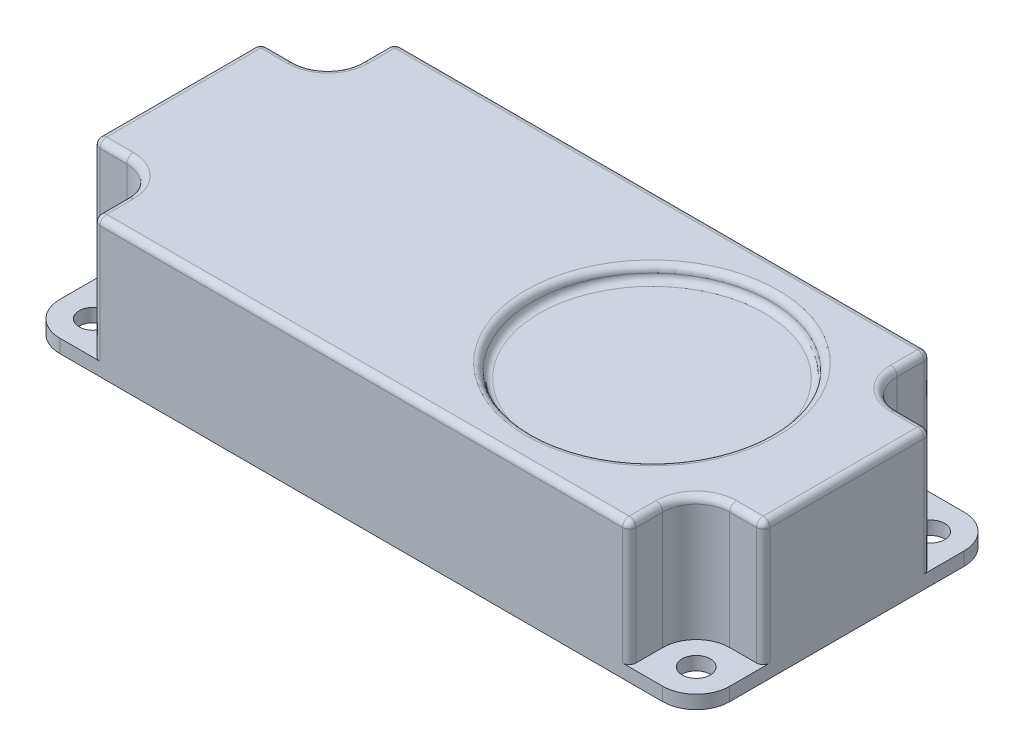
SolidWorks part; units mm, degrees
ref_plane "前视基准面" through (0, 0, 0) normal (0, 0, 1) x (1, 0, 0)
ref_plane "上视基准面" through (0, 0, 0) normal (0, 1, 0) x (1, 0, 0)
ref_plane "右视基准面" through (0, 0, 0) normal (1, 0, 0) x (0, 0, -1)
other "Configuration Table"
sketch "草图1" plane through (0, 0, 0) normal (0, 1, 0) x (1, 0, 0)
  line L1 (-45, -22.5) -> (45, -22.5)
  line L2 (-50, -17.5) -> (-50, 17.5)
  line L3 (-45, 22.5) -> (45, 22.5)
  line L4 (50, -17.5) -> (50, 17.5)
  line L5 (-50, -22.5) -> (50, 22.5) construction
  line L6 (-50, 22.5) -> (50, -22.5) construction
  arc A0 (45, -22.5) -> (50, -17.5) centre (45, -17.5) ccw
  arc A1 (-45, -22.5) -> (-50, -17.5) centre (-45, -17.5) cw
  arc A2 (-50, 17.5) -> (-45, 22.5) centre (-45, 17.5) cw
  arc A3 (45, 22.5) -> (50, 17.5) centre (45, 17.5) cw
  point P0 (0, 0)
  dimension "D3" = 5
  dimension "D1" = 100
  dimension "D2" = 45
extrude "凸台-拉伸1" add sketch "草图1" along normal blind 2 contours L4 A3 L3 A2 L2 A1 L1 A0
sketch "草图2" plane through (0, 2, 0) normal (0, 1, 0) x (1, 0, 0)
  line L0 (-40, 22.5) -> (-40, 17.5)
  line L1 (-40, -22.5) -> (40, -22.5)
  line L2 (-50, -12.5) -> (-50, 12.5)
  line L3 (-40, 22.5) -> (40, 22.5)
  line L4 (50, -12.5) -> (50, 12.5)
  line L7 (40, 22.5) -> (40, 17.5)
  line L8 (-50, 12.5) -> (-45, 12.5)
  line L9 (50, -12.5) -> (45, -12.5)
  line L10 (40, -17.5) -> (40, -22.5)
  line L11 (45, 12.5) -> (50, 12.5)
  line L14 (-40, -17.5) -> (-40, -22.5)
  line L15 (-45, -12.5) -> (-50, -12.5)
  arc A0 (40, 17.5) -> (45, 12.5) centre (45, 17.5) ccw
  arc A1 (45, -12.5) -> (40, -17.5) centre (45, -17.5) ccw
  arc A2 (-40, -17.5) -> (-45, -12.5) centre (-45, -17.5) ccw
  arc A3 (-45, 12.5) -> (-40, 17.5) centre (-45, 17.5) ccw
  point P0 (0, 0)
extrude "凸台-拉伸3" add sketch "草图2" along normal blind 18.5
fillet "圆角1" radius 1 24 edges at (47.5, 20.5, -12.5) (50, 20.5, 0) (47.5, 20.5, 12.5) (41.4645, 20.5, 13.9645) (40, 20.5, 20) (0, 20.5, 22.5) (-40, 20.5, 20) (-41.4645, 20.5, 13.9645) (-47.5, 20.5, 12.5) (-50, 20.5, 0) (-47.5, 20.5, -12.5) (-41.4645, 20.5, -13.9645) (-40, 20.5, -20) (0, 20.5, -22.5) (40, 20.5, -20) (41.4645, 20.5, -13.9645) (50, 11.25, -12.5) (40, 11.25, -22.5) (-40, 11.25, -22.5) (-50, 11.25, -12.5) (-40, 11.25, 22.5) (-50, 11.25, 12.5) (40, 11.25, 22.5) (50, 11.25, 12.5)
sketch "草图4" plane through (0, 20.5, 0) normal (0, 1, 0) x (1, 0, 0)
  circle A0 centre (20.8924, 0) radius 17.8213
extrude "切除-拉伸1" cut sketch "草图4" against normal blind 2
fillet "圆角2" radius 1 2 edges at (20.8924, 18.5, 17.8213) (20.8924, 20.5, 17.8213)
sketch "草图5" plane through (0, 2, 0) normal (0, 1, 0) x (1, 0, 0)
  circle A0 centre (-45, 17.5) radius 2.1
  circle A1 centre (45, 17.5) radius 2.1
  circle A2 centre (45, -17.5) radius 2.1
  circle A3 centre (-45, -17.5) radius 2.1
  dimension "D1" = 4.2
  dimension "D2" = 4.2
  dimension "D3" = 4.2
  dimension "D4" = 4.2
extrude "切除-拉伸2" cut sketch "草图5" against normal blind 2
